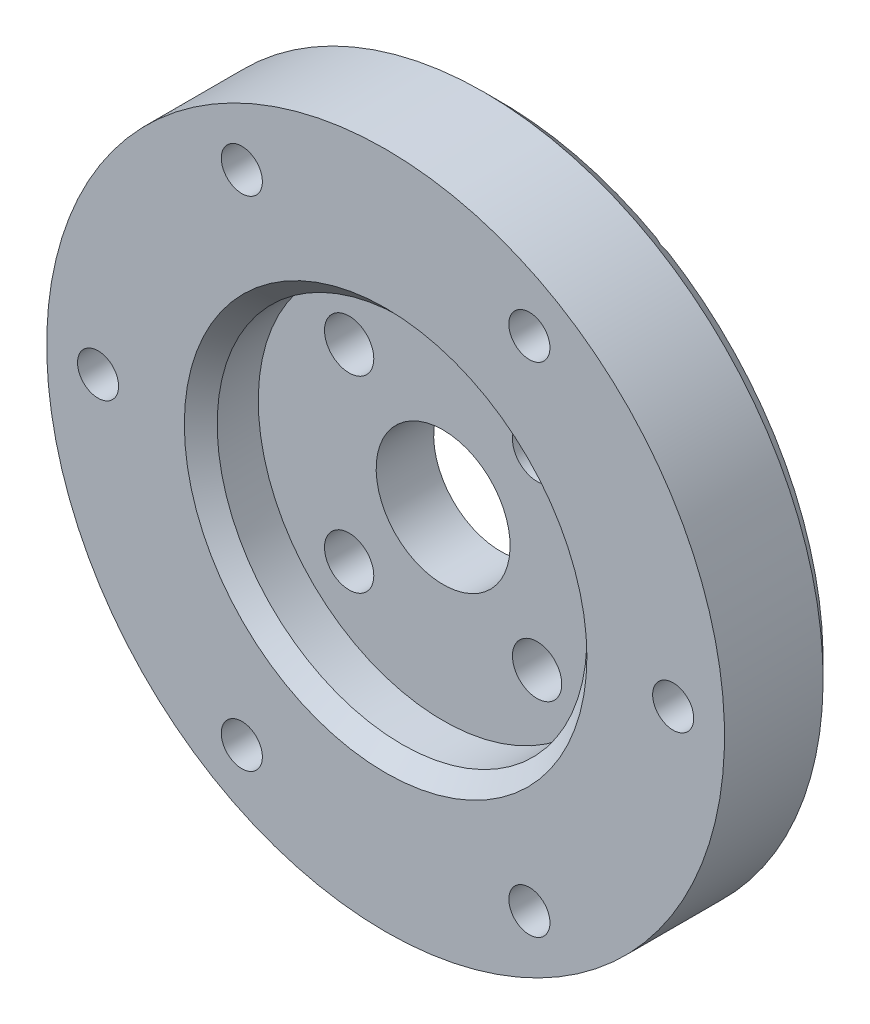
SolidWorks part; units mm, degrees
ref_plane "前视基准面" through (0, 0, 0) normal (0, 0, 1) x (1, 0, 0)
ref_plane "上视基准面" through (0, 0, 0) normal (0, 1, 0) x (1, 0, 0)
ref_plane "右视基准面" through (0, 0, 0) normal (1, 0, 0) x (0, 0, -1)
sketch "草图1" plane through (0, 0, 0) normal (1, 0, 0) x (0, 0, -1)
  line L0 (0, 41.25) -> (0, 22.5)
  line L1 (0, 41.25) -> (14, 41.25)
  line L5 (14, 0) -> (7, 0) construction
  line L6 (0, 22.5) -> (7, 22.5)
  line L8 (7, 8.15) -> (14, 8.15)
  line L9 (7, 22.5) -> (7, 8.15)
  line L10 (14, 8.15) -> (14, 41.25)
  dimension "D1" = 41.25
  dimension "D4" = 7
  dimension "D5" = 22.5
  dimension "D6" = 7
  dimension "D7" = 8.15
revolve "旋转1" add sketch "草图1" angle 360 about L5
sketch "草图2" plane through (0, 0, 0) normal (0, 0, 1) x (1, 0, 0)
  line L1 (-11.4375, -11.4375) -> (11.4375, -11.4375) construction
  line L2 (-11.4375, -11.4375) -> (-11.4375, 11.4375) construction
  line L3 (-11.4375, 11.4375) -> (11.4375, 11.4375) construction
  line L4 (11.4375, -11.4375) -> (11.4375, 11.4375) construction
  line L5 (-11.4375, -11.4375) -> (11.4375, 11.4375) construction
  line L6 (-11.4375, 11.4375) -> (11.4375, -11.4375) construction
  line L7 (17.5, 30.3109) -> (-17.5, 30.3109) construction
  line L8 (-17.5, 30.3109) -> (-35, 0) construction
  line L9 (-35, 0) -> (-17.5, -30.3109) construction
  line L10 (-17.5, -30.3109) -> (17.5, -30.3109) construction
  line L11 (17.5, -30.3109) -> (35, 0) construction
  line L12 (35, 0) -> (17.5, 30.3109) construction
  circle A0 centre (0, 0) radius 30.3109 construction
  circle A1 centre (-17.5, 30.3109) radius 2.5
  circle A2 centre (17.5, 30.3109) radius 2.5
  circle A3 centre (35, 0) radius 2.5
  circle A4 centre (17.5, -30.3109) radius 2.5
  circle A5 centre (-17.5, -30.3109) radius 2.5
  circle A6 centre (-35, 0) radius 2.5
  circle A7 centre (-11.4375, 11.4375) radius 3
  circle A8 centre (11.4375, 11.4375) radius 3
  circle A9 centre (11.4375, -11.4375) radius 3
  circle A10 centre (-11.4375, -11.4375) radius 3
  circle A11 centre (-11.4375, 11.4375) radius 5.25 construction
  point P0 (0, 0)
  dimension "D2" = 5
  dimension "D4" = 6
  dimension "D5" = 10.5
  dimension "D1" = 70
  dimension "D3" = 32.35
extrude "切除-拉伸1" cut sketch "草图2" against normal through all
sketch "草图3" plane through (0, 0, -14) normal (0, 0, -1) x (-1, 0, 0)
  line L1 (-12.8235, 30.3109) -> (-15.1617, 34.3609)
  line L2 (-15.1617, 34.3609) -> (-19.8383, 34.3609)
  line L3 (-19.8383, 34.3609) -> (-22.1765, 30.3109)
  line L4 (-22.1765, 30.3109) -> (-19.8383, 26.2609)
  line L5 (-19.8383, 26.2609) -> (-15.1617, 26.2609)
  line L6 (-15.1617, 26.2609) -> (-12.8235, 30.3109)
  line L7 (19.8383, 26.2609) -> (22.1765, 30.3109)
  line L8 (22.1765, 30.3109) -> (19.8383, 34.3609)
  line L9 (19.8383, 34.3609) -> (15.1617, 34.3609)
  line L10 (15.1617, 34.3609) -> (12.8235, 30.3109)
  line L11 (12.8235, 30.3109) -> (15.1617, 26.2609)
  line L12 (15.1617, 26.2609) -> (19.8383, 26.2609)
  line L13 (32.6617, -4.05) -> (37.3383, -4.05)
  line L14 (37.3383, -4.05) -> (39.6765, 0)
  line L15 (39.6765, 0) -> (37.3383, 4.05)
  line L16 (37.3383, 4.05) -> (32.6617, 4.05)
  line L17 (32.6617, 4.05) -> (30.3235, 0)
  line L18 (30.3235, 0) -> (32.6617, -4.05)
  line L19 (19.8383, -26.2609) -> (15.1617, -26.2609)
  line L20 (15.1617, -26.2609) -> (12.8235, -30.3109)
  line L21 (12.8235, -30.3109) -> (15.1617, -34.3609)
  line L22 (15.1617, -34.3609) -> (19.8383, -34.3609)
  line L23 (19.8383, -34.3609) -> (22.1765, -30.3109)
  line L24 (22.1765, -30.3109) -> (19.8383, -26.2609)
  line L25 (-15.1617, -26.2609) -> (-19.8383, -26.2609)
  line L26 (-19.8383, -26.2609) -> (-22.1765, -30.3109)
  line L27 (-22.1765, -30.3109) -> (-19.8383, -34.3609)
  line L28 (-19.8383, -34.3609) -> (-15.1617, -34.3609)
  line L29 (-15.1617, -34.3609) -> (-12.8235, -30.3109)
  line L30 (-12.8235, -30.3109) -> (-15.1617, -26.2609)
  line L31 (-32.6617, 4.05) -> (-37.3383, 4.05)
  line L32 (-37.3383, 4.05) -> (-39.6765, 0)
  line L33 (-39.6765, 0) -> (-37.3383, -4.05)
  line L34 (-37.3383, -4.05) -> (-32.6617, -4.05)
  line L35 (-32.6617, -4.05) -> (-30.3235, 0)
  line L36 (-30.3235, 0) -> (-32.6617, 4.05)
  circle A0 centre (-17.5, 30.3109) radius 4.05 construction
  circle A1 centre (17.5, 30.3109) radius 4.05 construction
  circle A2 centre (35, 0) radius 4.05 construction
  circle A3 centre (17.5, -30.3109) radius 4.05 construction
  circle A4 centre (-17.5, -30.3109) radius 4.05 construction
  circle A5 centre (-35, 0) radius 4.05 construction
  dimension "D1" = 8.1
extrude "切除-拉伸2" cut sketch "草图3" against normal offset from surface (8 mm away) 6 up to face at (-32.5, 0, 0)
chamfer "倒角1" distance 2 angle 45 2 edges at (0, 22.5, 0) (0, 41.25, -14)
